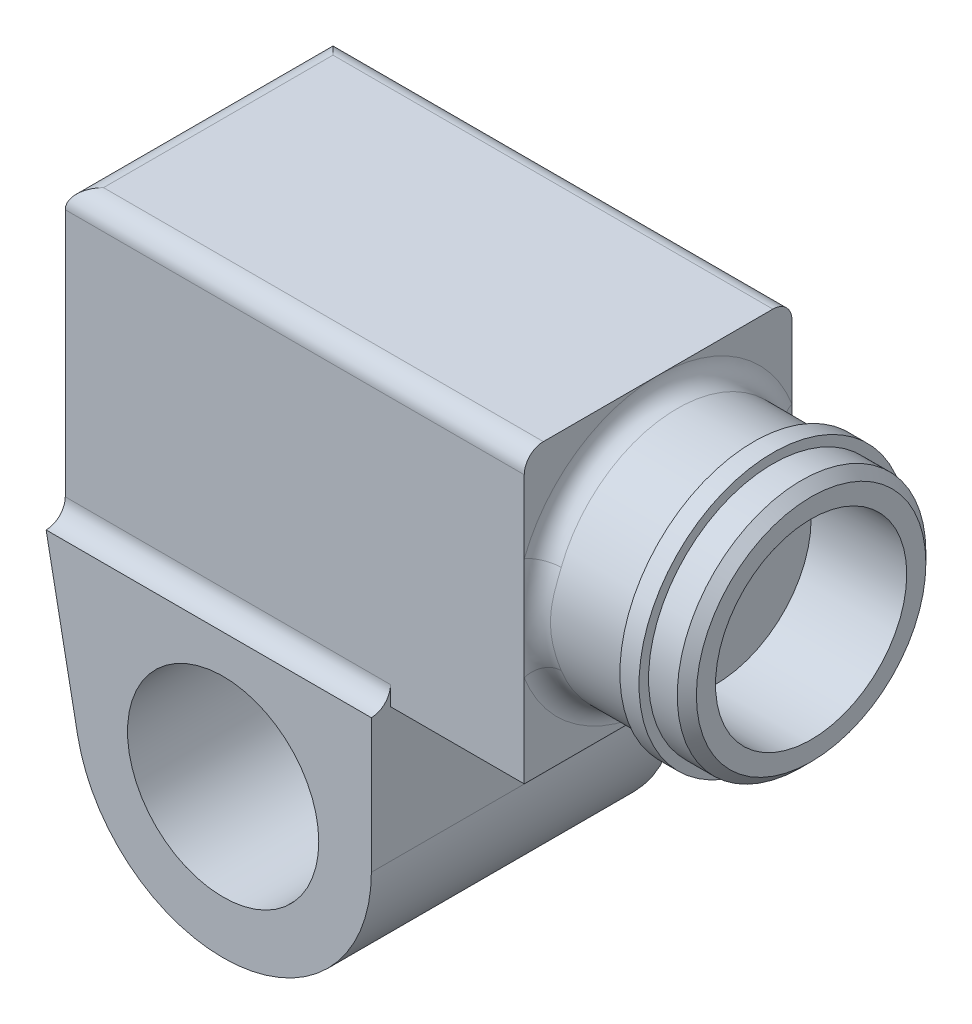
SolidWorks part; units mm, degrees
ref_plane "Front Plane" through (0, 0, 0) normal (0, 0, 1) x (1, 0, 0)
ref_plane "Top Plane" through (0, 0, 0) normal (0, 1, 0) x (1, 0, 0)
ref_plane "Right Plane" through (0, 0, 0) normal (1, 0, 0) x (0, 0, -1)
sketch "Sketch1" plane through (0, 0, 0) normal (0, 1, 0) x (1, 0, 0)
  line L1 (-120, -70) -> (120, -70)
  line L2 (-120, -70) -> (-120, 70)
  line L3 (-120, 70) -> (120, 70)
  line L4 (120, -70) -> (120, 70)
  line L5 (-120, -70) -> (120, 70) construction
  line L6 (-120, 70) -> (120, -70) construction
  point P0 (0, 0)
  dimension "D1" = 240
  dimension "D2" = 140
extrude "Boss-Extrude1" add sketch "Sketch1" along normal blind 150
sketch "Sketch2" plane through (120, 0, 0) normal (1, 0, 0) x (0, 0, -1)
  line L0 (-70, 0) -> (70, 150) construction
  line L1 (70, 150) -> (70, 0) construction
  circle A0 centre (0, 75) radius 65
  point P7 (70, 150)
  dimension "D1" = 130
extrude "Boss-Extrude2" add sketch "Sketch2" along normal blind 50
sketch "Sketch3" plane through (170, 0, 0) normal (1, 0, 0) x (0, 0, -1)
  circle A0 centre (0, 75) radius 70
  dimension "D1" = 140
extrude "Boss-Extrude3" add sketch "Sketch3" along normal blind 10
sketch "Sketch4" plane through (0, 0, 0) normal (0, 0, 1) x (1, 0, 0)
  line L0 (-27.4428, 0) -> (-27.4428, -70) construction
  line L1 (-120, 0) -> (120, 0) construction
  line L2 (50.0572, -70) -> (50.0572, 0)
  line L3 (50.0572, 0) -> (-120, 0)
  line L4 (-120, 0) -> (-103.5189, -84.7877)
  line L5 (-120, 150) -> (-120, 0) construction
  arc A0 (-103.5189, -84.7877) -> (50.0572, -70) centre (-27.4428, -70) ccw
  circle A1 centre (-27.4428, -70) radius 50
  dimension "D1" = 155
  dimension "D2" = 100
  dimension "D3" = 191
  dimension "D4" = 70
extrude "Boss-Extrude4" add sketch "Sketch4" along normal mid plane 160
fillet "Fillet1" radius 10 3 edges at (-34.9714, 0, -70) (120, 75, -65) (-34.9714, 0, 70)
extrude "Boss-Extrude5" add sketch "Sketch2<2>" along normal blind 20 from surface starting at face at (180, 75, -70)
sketch "Sketch2<2>" plane through (120, 0, 0) normal (1, 0, 0) x (0, 0, -1) same geometry as "Sketch2"
fillet "Fillet2" radius 10 3 edges at (0, 150, -70) (-120, 150, 0) (0, 150, 70)
sketch "Sketch5" plane through (200, 0, 0) normal (1, 0, 0) x (0, 0, -1)
  circle A0 centre (0, 75) radius 50
  dimension "D1" = 100
extrude "Cut-Extrude1" cut sketch "Sketch5" against normal blind 50
chamfer "Chamfer1" distance 5 angle 45 1 edges at (200, 75, -65)
